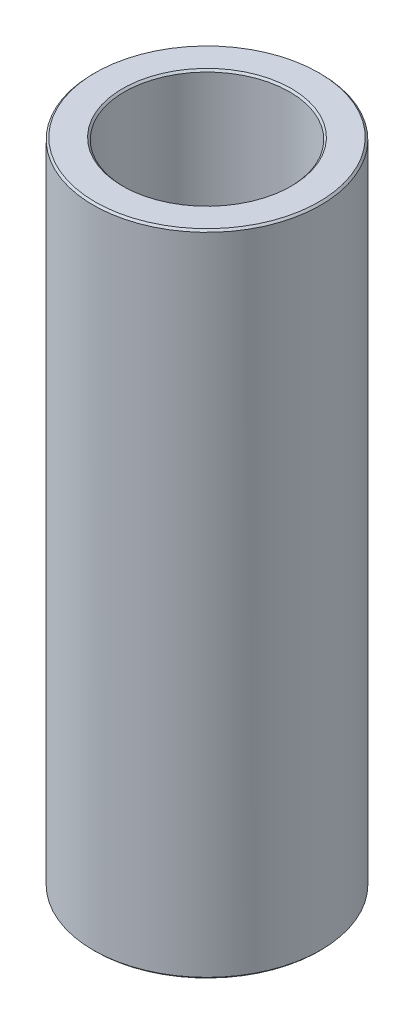
SolidWorks part; units mm, degrees
ref_plane "Front Plane" through (0, 0, 0) normal (0, 0, 1) x (1, 0, 0)
ref_plane "Top Plane" through (0, 0, 0) normal (0, 1, 0) x (1, 0, 0)
ref_plane "Right Plane" through (0, 0, 0) normal (1, 0, 0) x (0, 0, -1)
sketch "Sketch1" plane through (0, 0, 0) normal (0, 1, 0) x (1, 0, 0)
  circle A0 centre (0, 0) radius 40
  dimension "SLEEVE_OD" = 80
extrude "Boss-Extrude1" add sketch "Sketch1" along normal blind 228.1984
sketch "Sketch2" plane through (0, 0, 0) normal (0, 1, 0) x (1, 0, 0)
  circle A0 centre (0, 0) radius 29.0477
  dimension "BORE_D" = 58.0953
extrude "Cut-Extrude1" cut sketch "Sketch2" along normal through all
chamfer "Chamfer1" distance 0.6557 angle 45 4 edges at (0, 228.1984, 29.0477) (0, 0, 29.0477) (0, 0, 40) (0, 228.1984, 40)
